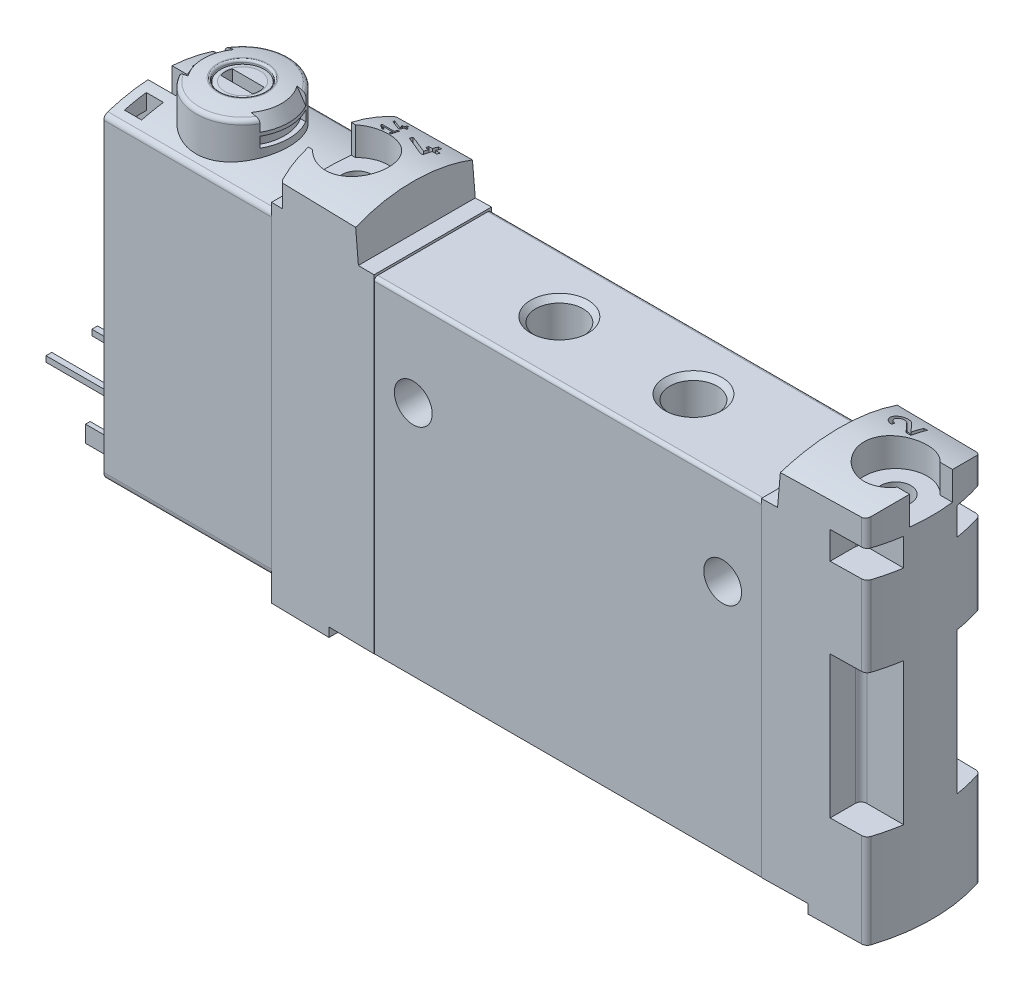
SolidWorks part; units mm, degrees
ref_plane "Front Plane" through (0, 0, 0) normal (0, 0, 1) x (1, 0, 0)
ref_plane "Top Plane" through (0, 0, 0) normal (0, 1, 0) x (1, 0, 0)
ref_plane "Right Plane" through (0, 0, 0) normal (1, 0, 0) x (0, 0, -1)
sketch "Sketch1" plane through (0, 0, 0) normal (1, 0, 0) x (0, 0, -1)
  line L0 (-5.1, 28.15) -> (-5.1, 0)
  line L1 (-5.1, 0) -> (5.1, 0)
  line L2 (5.1, 0) -> (5.1, 28.15)
  line L3 (4.8, 28.45) -> (-4.8, 28.45)
  arc A0 (5.1, 28.15) -> (4.8, 28.45) centre (4.8, 28.15) ccw
  arc A1 (-4.8, 28.45) -> (-5.1, 28.15) centre (-4.8, 28.15) ccw
extrude "Boss-Extrude1" add sketch "Sketch1" against normal blind 16.9 and the other way blind 16.9
sketch "Sketch2" plane through (0, 0, 0) normal (0, 0, 1) x (1, 0, 0)
  circle A0 centre (-13.5, 20.65) radius 1.65
extrude "Cut-Extrude1" cut sketch "Sketch2" along normal blind 6 and the other way blind 6
sketch "Sketch3" plane through (0, 0, 0) normal (0, 0, 1) x (1, 0, 0)
  circle A0 centre (13.5, 20.65) radius 1.65
extrude "Cut-Extrude2" cut sketch "Sketch3" along normal blind 6 and the other way blind 6
ref_plane "Plane1" through (0, 0, 0) normal (0, 0, 1) x (1, 0, 0)
ref_plane "Plane2" through (0, 0, -1.55) normal (0, 0, 1) x (1, 0, 0)
ref_plane "Plane3" through (0, 0, 1.55) normal (0, 0, 1) x (1, 0, 0)
ref_plane "Plane4" through (-13.4, 0, 0) normal (1, 0, 0) x (0, 0, -1)
ref_plane "Plane5" through (0, 0, 1.495) normal (0, 0, 1) x (1, 0, 0)
ref_plane "Plane6" through (0, 0, -2.205) normal (0, 0, 1) x (1, 0, 0)
hole_wizard "Hole1" positions "Sketch5" profile "Sketch4" legacy
sketch "Sketch5" plane through (0, 0, 0) normal (0, -1, 0) x (-1, 0, 0)
  point P0 (-11, 0)
sketch "Sketch4" plane through (11, 0, 0) normal (1, 0, 0) x (0, 0, -1)
  line L0 (0, 0) -> (0, 13.5)
  line L1 (0, 13.5) -> (2.067, 13.5)
  line L2 (2.067, 13.5) -> (2.067, 0.433)
  line L3 (2.067, 0.433) -> (2.5, 0)
  line L4 (2.5, 0) -> (0, 0)
  line L5 (0, -6.4453) -> (0, 115.525) construction
  line L6 (-2.067, 0.433) -> (-2.5, 0) construction
  dimension "Diameter" = 4.134
  dimension "Depth" = 13.5
  dimension "C-Sink Angle" = 90
  dimension "C-Sink Diameter" = 5
cosmetic thread "Cosmetic Thread1" parameters "D1"=5, "D2"=5
hole_wizard "Hole2" positions "Sketch7" profile "Sketch6" legacy
sketch "Sketch7" plane through (0, 0, 0) normal (0, -1, 0) x (-1, 0, 0)
  point P0 (0, 0)
sketch "Sketch6" plane through (0, 0, 0) normal (1, 0, 0) x (0, 0, -1)
  line L0 (0, 0) -> (0, 19.9934)
  line L1 (0, 19.9934) -> (2.067, 18.8)
  line L2 (2.067, 18.8) -> (2.067, 0.433)
  line L3 (2.067, 0.433) -> (2.5, 0)
  line L4 (2.5, 0) -> (0, 0)
  line L5 (0, -14.3089) -> (0, 102.4216) construction
  line L6 (0, 19.9934) -> (-2.067, 18.8) construction
  line L7 (-2.067, 0.433) -> (-2.5, 0) construction
  dimension "Diameter" = 4.134
  dimension "Depth" = 18.8
  dimension "C-Sink Diameter" = 5
  dimension "C-Sink Angle" = 90
  dimension "Drill Angle" = 120
cosmetic thread "Cosmetic Thread2" parameters "D1"=5, "D2"=5
hole_wizard "Hole3" positions "Sketch9" profile "Sketch8" legacy
sketch "Sketch9" plane through (0, 0, 0) normal (0, -1, 0) x (-1, 0, 0)
  point P0 (11, 0)
sketch "Sketch8" plane through (-11, 0, 0) normal (1, 0, 0) x (0, 0, -1)
  line L0 (0, 0) -> (0, 13.5)
  line L1 (0, 13.5) -> (2.067, 13.5)
  line L2 (2.067, 13.5) -> (2.067, 0.433)
  line L3 (2.067, 0.433) -> (2.5, 0)
  line L4 (2.5, 0) -> (0, 0)
  line L5 (0, -6.4453) -> (0, 115.525) construction
  line L6 (-2.067, 0.433) -> (-2.5, 0) construction
  dimension "Diameter" = 4.134
  dimension "Depth" = 13.5
  dimension "C-Sink Angle" = 90
  dimension "C-Sink Diameter" = 5
cosmetic thread "Cosmetic Thread3" parameters "D1"=5, "D2"=5
hole_wizard "Hole4" positions "Sketch11" profile "Sketch10" legacy
sketch "Sketch11" plane through (0, 28.45, 0) normal (0, 1, 0) x (1, 0, 0)
  point P0 (-5.85, 0)
sketch "Sketch10" plane through (-5.85, 28.45, 0) normal (1, 0, 0) x (0, 0, 1)
  line L0 (0, 0) -> (0, 6.6)
  line L1 (0, 6.6) -> (2.067, 6.6)
  line L2 (2.067, 6.6) -> (2.067, 0.433)
  line L3 (2.067, 0.433) -> (2.5, 0)
  line L4 (2.5, 0) -> (0, 0)
  line L5 (0, -6.4453) -> (0, 115.525) construction
  line L6 (-2.067, 0.433) -> (-2.5, 0) construction
  dimension "Diameter" = 4.134
  dimension "Depth" = 6.6
  dimension "C-Sink Angle" = 90
  dimension "C-Sink Diameter" = 5
cosmetic thread "Cosmetic Thread4" parameters "D1"=5.8, "D2"=5
hole_wizard "Hole5" positions "Sketch13" profile "Sketch12" legacy
sketch "Sketch13" plane through (0, 28.45, 0) normal (0, 1, 0) x (1, 0, 0)
  point P0 (5.85, 0)
sketch "Sketch12" plane through (5.85, 28.45, 0) normal (1, 0, 0) x (0, 0, 1)
  line L0 (0, 0) -> (0, 6.6)
  line L1 (0, 6.6) -> (2.067, 6.6)
  line L2 (2.067, 6.6) -> (2.067, 0.433)
  line L3 (2.067, 0.433) -> (2.5, 0)
  line L4 (2.5, 0) -> (0, 0)
  line L5 (0, -6.4453) -> (0, 115.525) construction
  line L6 (-2.067, 0.433) -> (-2.5, 0) construction
  dimension "Diameter" = 4.134
  dimension "Depth" = 6.6
  dimension "C-Sink Angle" = 90
  dimension "C-Sink Diameter" = 5
cosmetic thread "Cosmetic Thread5" parameters "D1"=5.8, "D2"=5
ref_plane "Plane7" through (0, 20.4, 0) normal (0, 1, 0) x (1, 0, 0)
ref_plane "Plane8" through (-11.06, 0, 0) normal (1, 0, 0) x (0, 0, -1)
ref_plane "Plane9" through (-4.15, 0, 0) normal (1, 0, 0) x (0, 0, -1)
ref_plane "Plane10" through (3.15, 0, 0) normal (1, 0, 0) x (0, 0, -1)
ref_plane "Plane11" through (0, 0, -3) normal (0, 0, 1) x (1, 0, 0)
hole_wizard "Hole6" positions "Sketch15" profile "Sketch14" legacy
sketch "Sketch15" plane through (0, 0, 0) normal (0, -1, 0) x (-1, 0, 0)
  point P0 (4.9, 3)
sketch "Sketch14" plane through (-4.9, 0, -3) normal (1, 0, 0) x (0, 0, -1)
  line L0 (0, 0) -> (0, 2.2217)
  line L1 (0, 2.2217) -> (1.25, 1.5)
  line L2 (1.25, 1.5) -> (1.25, 0)
  line L4 (1.25, 0) -> (0, 0)
  line L6 (0, 2.2217) -> (-1.25, 1.5) construction
  line L7 (0, -4.2442) -> (0, 117.3081) construction
  dimension "Diameter" = 2.5
  dimension "Depth" = 1.5
  dimension "Drill Angle" = 120
ref_plane "Plane12" through (0, -0.8, 0) normal (0, 1, 0) x (1, 0, 0)
sketch "Sketch16" plane through (0, -0.8, 0) normal (0, 1, 0) x (1, 0, 0)
  line L0 (16.9, 5.125) -> (16.9, -5.125)
  line L1 (16.9, -5.125) -> (25.5086, -4.9747)
  line L2 (25.5086, 4.9747) -> (16.9, 5.125)
  arc A0 (25.5086, -4.9747) -> (25.976, -4.6275) centre (25.4999, -4.4748) ccw
  arc A1 (25.976, -4.6275) -> (25.976, 4.6275) centre (11.55, 0) ccw
  arc A2 (25.976, 4.6275) -> (25.5086, 4.9747) centre (25.4999, 4.4748) ccw
extrude "Boss-Extrude2" add sketch "Sketch16" along normal blind 33.1
ref_plane "Plane13" through (0, 7.4, 0) normal (0, 1, 0) x (1, 0, 0)
sketch "Sketch17" plane through (0, 7.4, 0) normal (0, 1, 0) x (1, 0, 0)
  line L0 (23.3, 2.325) -> (27.8, 2.325)
  line L1 (27.8, 2.325) -> (27.8, -2.325)
  line L2 (27.8, -2.325) -> (23.3, -2.325)
  line L3 (22.8, -2.825) -> (22.8, -5.125)
  line L4 (22.8, -5.125) -> (29.8, -5.125)
  line L5 (29.8, -5.125) -> (29.8, 5.125)
  line L6 (29.8, 5.125) -> (22.8, 5.125)
  line L7 (22.8, 5.125) -> (22.8, 2.825)
  arc A0 (22.8, 2.825) -> (23.3, 2.325) centre (23.3, 2.825) ccw
  arc A1 (23.3, -2.325) -> (22.8, -2.825) centre (23.3, -2.825) ccw
extrude "Cut-Extrude3" cut sketch "Sketch17" along normal blind 12.4
ref_plane "Plane14" through (0, 26.8, 0) normal (0, 1, 0) x (1, 0, 0)
sketch "Sketch18" plane through (0, 26.8, 0) normal (0, 1, 0) x (1, 0, 0)
  line L0 (23.3, 2.325) -> (27.8, 2.325)
  line L1 (27.8, 2.325) -> (27.8, -2.325)
  line L2 (27.8, -2.325) -> (23.3, -2.325)
  line L3 (22.8, -2.825) -> (22.8, -5.125)
  line L4 (22.8, -5.125) -> (29.8, -5.125)
  line L5 (29.8, -5.125) -> (29.8, 5.125)
  line L6 (29.8, 5.125) -> (22.8, 5.125)
  line L7 (22.8, 5.125) -> (22.8, 2.825)
  arc A0 (22.8, 2.825) -> (23.3, 2.325) centre (23.3, 2.825) ccw
  arc A1 (23.3, -2.325) -> (22.8, -2.825) centre (23.3, -2.825) ccw
extrude "Cut-Extrude4" cut sketch "Sketch18" along normal blind 2.4
ref_plane "Plane15" through (0, 28.45, 0) normal (0, 1, 0) x (1, 0, 0)
sketch "Sketch19" plane through (0, 0, 0) normal (1, 0, 0) x (0, 0, -1)
  line L0 (5.125, 31.3973) -> (5.125, 37)
  line L1 (5.125, 37) -> (-5.125, 37)
  line L2 (-5.125, 37) -> (-5.125, 31.3973)
  arc A0 (-5.125, 31.3973) -> (5.125, 31.3973) centre (0, 17.3) cw
ref_plane "Plane16" through (0, 29.5, 0) normal (0, 1, 0) x (1, 0, 0)
sketch "Sketch20" plane through (0, 0, 0) normal (0, 0, 1) x (1, 0, 0)
  line L0 (13.29, 34.65) -> (13.29, 28.65)
  line L1 (13.29, 28.65) -> (18.29, 28.65)
  line L2 (18.29, 28.65) -> (18.8149, 34.65)
  line L3 (18.8149, 34.65) -> (13.29, 34.65)
extrude "Cut-Extrude5" cut sketch "Sketch20" along normal blind 6 and the other way blind 6
ref_plane "Plane17" through (21.86, 0, 0) normal (1, 0, 0) x (0, 0, -1)
ref_plane "Plane18" through (0, 14.6, 0) normal (0, 1, 0) x (1, 0, 0)
ref_plane "Plane19" through (40.24, 0, 0) normal (1, 0, 0) x (0, 0, -1)
ref_plane "Plane20" through (0, 10.65, 0) normal (0, 1, 0) x (1, 0, 0)
sketch "Sketch21" plane through (0, 0, 0) normal (0, 0, 1) x (1, 0, 0)
  line L0 (23.5, 29.7) -> (24.825, 29.7)
  line L1 (24.825, 29.7) -> (24.625, -0.8)
  line L2 (24.625, -0.8) -> (23.5, -0.8)
  line L3 (23.5, -0.8) -> (23.5, 29.7)
  line L4 (23.5, -0.8) -> (23.5, 29.7) construction
revolve "Cut-Revolve1" cut sketch "Sketch21" angle 360 about L4 reverse direction yes
ref_plane "Plane21" through (0, 29.7, 0) normal (0, 1, 0) x (1, 0, 0)
sketch "Sketch22" plane through (0, 29.7, 0) normal (0, 1, 0) x (1, 0, 0)
  line L0 (25.5117, -1.875) -> (28.5, -1.875)
  line L1 (28.5, -1.875) -> (28.5, 1.875)
  line L2 (28.5, 1.875) -> (25.5117, 1.875)
  arc A0 (25.5117, 1.875) -> (25.5117, -1.875) centre (23.5, 0) ccw
extrude "Cut-Extrude6" cut sketch "Sketch22" along normal blind 4
ref_plane "Plane22" through (0, -0.8, 0) normal (0, 1, 0) x (1, 0, 0)
sketch "Sketch23" plane through (0, -0.8, 0) normal (0, 1, 0) x (1, 0, 0)
  line L0 (-26, -4.9662) -> (-16.9, -5.125)
  line L1 (-16.9, -5.125) -> (-16.9, 5.125)
  line L2 (-16.9, 5.125) -> (-26, 4.9662)
  line L3 (-26, 4.9662) -> (-26, -4.9662)
extrude "Boss-Extrude3" add sketch "Sketch23" along normal blind 33.1
extrude "Cut-Extrude7" cut sketch "Sketch19" along normal blind 32 and the other way blind 32
sketch "Sketch24" plane through (0, 29.7, 0) normal (0, 1, 0) x (1, 0, 0)
  line L0 (-26.5, -1.875) -> (-25.5117, -1.875)
  line L1 (-25.5117, 1.875) -> (-26.5, 1.875)
  line L2 (-26.5, 1.875) -> (-26.5, -1.875)
  arc A0 (-25.5117, -1.875) -> (-25.5117, 1.875) centre (-23.5, 0) ccw
extrude "Cut-Extrude8" cut sketch "Sketch24" along normal blind 4
sketch "Sketch25" plane through (0, 0, 0) normal (0, 0, 1) x (1, 0, 0)
  line L0 (-18.8149, 34.65) -> (-18.29, 28.65)
  line L1 (-18.29, 28.65) -> (-13.29, 28.65)
  line L2 (-13.29, 28.65) -> (-13.29, 34.65)
  line L3 (-13.29, 34.65) -> (-18.8149, 34.65)
extrude "Cut-Extrude9" cut sketch "Sketch25" along normal blind 6 and the other way blind 6
sketch "Sketch26" plane through (0, 29.5, 0) normal (0, 1, 0) x (1, 0, 0)
  line L0 (-31.04, -6.125) -> (-21.04, -6.125)
  line L1 (-21.04, -6.125) -> (-21.04, -5.125)
  line L2 (-21.04, -5.125) -> (-24.7731, -5.0598)
  line L3 (-24.7731, 5.0598) -> (-21.04, 5.125)
  line L4 (-21.04, 5.125) -> (-21.04, 6.125)
  line L5 (-21.04, 6.125) -> (-31.04, 6.125)
  line L6 (-31.04, 6.125) -> (-31.04, -6.125)
  arc A0 (-24.7731, -5.0598) -> (-25.239, -4.7172) centre (-24.7643, -4.5599) cw
  arc A1 (-25.239, -4.7172) -> (-25.239, 4.7172) centre (-11, 0) cw
  arc A2 (-25.239, 4.7172) -> (-24.7731, 5.0598) centre (-24.7643, 4.5599) cw
extrude "Cut-Extrude10" cut sketch "Sketch26" along normal blind 5
sketch "Sketch27" plane through (0, 0, 0) normal (0, 0, 1) x (1, 0, 0)
  line L0 (-20.9, -2) -> (20.9, -2)
  line L1 (20.9, -2) -> (20.9, 0)
  line L2 (20.9, 0) -> (-20.9, 0)
  line L3 (-20.9, 0) -> (-20.9, -2)
extrude "Cut-Extrude11" cut sketch "Sketch27" along normal blind 8 and the other way blind 8
ref_plane "Plane23" through (-21.86, 0, 0) normal (1, 0, 0) x (0, 0, -1)
sketch "Sketch28" plane through (-21.86, 0, 0) normal (1, 0, 0) x (0, 0, -1)
  line L0 (-4.2, 1) -> (4.2, 1)
  line L1 (4.9, 1.7) -> (4.9, 28.3163)
  line L2 (-4.9, 28.3163) -> (-4.9, 1.7)
  arc A0 (-4.9, 1.7) -> (-4.2, 1) centre (-4.2, 1.7) ccw
  arc A1 (4.2, 1) -> (4.9, 1.7) centre (4.2, 1.7) ccw
  arc A2 (4.9, 28.3163) -> (4.5517, 28.7927) centre (4.4, 28.3163) ccw
  arc A3 (4.5517, 28.7927) -> (-4.5517, 28.7927) centre (0, 14.5) ccw
  arc A4 (-4.5517, 28.7927) -> (-4.9, 28.3163) centre (-4.4, 28.3163) ccw
extrude "Boss-Extrude4" add sketch "Sketch28" against normal blind 21.34
ref_plane "Plane24" through (-40.7, 0, 0) normal (1, 0, 0) x (0, 0, -1)
sketch "Sketch29" plane through (-40.7, 0, 0) normal (1, 0, 0) x (0, 0, -1)
  line L0 (-4.9, 31) -> (-4.9, 1)
  line L1 (-4.9, 1) -> (4.9, 1)
  line L2 (4.9, 1) -> (4.9, 31)
  line L3 (4.9, 31) -> (-4.9, 31)
  line L4 (-4, 2.2) -> (-3.55, 1.75)
  line L5 (-3.55, 1.75) -> (3.55, 1.75)
  line L6 (3.55, 1.75) -> (4, 2.2)
  line L7 (4, 2.2) -> (4, 3.65)
  line L8 (4, 3.65) -> (3.6, 3.65)
  line L9 (3.6, 3.65) -> (3.6, 2.95)
  line L10 (3.1, 2.45) -> (-3.1, 2.45)
  line L11 (-3.6, 2.95) -> (-3.6, 3.65)
  line L12 (-3.6, 3.65) -> (-4, 3.65)
  line L13 (-4, 3.65) -> (-4, 2.2)
  arc A0 (3.6, 2.95) -> (3.1, 2.45) centre (3.1, 2.95) cw
  arc A1 (-3.1, 2.45) -> (-3.6, 2.95) centre (-3.1, 2.95) cw
extrude "Cut-Extrude12" cut sketch "Sketch29" against normal blind 6
sketch "Sketch30" plane through (0, 0, 0) normal (0, 0, 1) x (1, 0, 0)
  line L0 (-43.2, 1.75) -> (-42.1277, 1.25)
  line L1 (-42.1277, 1.25) -> (-41.9, 1.25)
  line L2 (-41.9, 1.25) -> (-41.9, 1.75)
  line L3 (-41.9, 1.75) -> (-43.2, 1.75)
extrude "Boss-Extrude5" add sketch "Sketch30" against normal blind 1.2 and the other way blind 1.2
sketch "Sketch31" plane through (-40.7, 0, 0) normal (1, 0, 0) x (0, 0, -1)
  line L0 (-3.15, 14.1) -> (-3.15, 3.1)
  line L1 (-3.15, 3.1) -> (3.15, 3.1)
  line L2 (3.15, 3.1) -> (3.15, 14.1)
  line L3 (3.15, 14.1) -> (-3.15, 14.1)
extrude "Boss-Extrude6" add sketch "Sketch31" against normal blind 1
sketch "Sketch32" plane through (-40.7, 0, 0) normal (1, 0, 0) x (0, 0, -1)
  line L0 (-2.25, 5.35) -> (-2.25, 4.85)
  line L1 (-2.25, 4.85) -> (-1.75, 4.85)
  line L2 (-1.75, 4.85) -> (-1.75, 5.35)
  line L3 (-1.75, 5.35) -> (-2.25, 5.35)
extrude "Boss-Extrude7" add sketch "Sketch32" against normal blind 7.7
sketch "Sketch33" plane through (-40.7, 0, 0) normal (1, 0, 0) x (0, 0, -1)
  line L0 (1.75, 5.35) -> (1.75, 4.85)
  line L1 (1.75, 4.85) -> (2.25, 4.85)
  line L2 (2.25, 4.85) -> (2.25, 5.35)
  line L3 (2.25, 5.35) -> (1.75, 5.35)
extrude "Boss-Extrude8" add sketch "Sketch33" against normal blind 7.7
ref_plane "Plane25" through (-40.24, 0, 0) normal (1, 0, 0) x (0, 0, -1)
hole_wizard "Hole7" positions "Sketch35" profile "Sketch34" legacy
sketch "Sketch35" plane through (0, 29.7, 0) normal (0, 1, 0) x (1, 0, 0)
  point P0 (-23.5, 0)
sketch "Sketch34" plane through (-23.5, 29.7, 0) normal (1, 0, 0) x (0, 0, 1)
  line L0 (0, 0) -> (0, 30.5)
  line L1 (0, 30.5) -> (1.125, 30.5)
  line L2 (1.125, 30.5) -> (1.325, 0)
  line L3 (1.325, 0) -> (0, 0)
  line L4 (0, 110) -> (0, -10) construction
  dimension "Minor Diameter" = 2.25
  dimension "Depth" = 30.5
  dimension "Major Diameter" = 2.65
sketch "Sketch36" plane through (0, 0, 0) normal (0, 0, 1) x (1, 0, 0)
  line L0 (-33.5, 32.665) -> (-29.45, 32.665)
  line L1 (-29.45, 32.665) -> (-29.45, 27.365)
  line L2 (-29.45, 27.365) -> (-33.5, 27.365)
  line L3 (-33.5, 27.365) -> (-33.5, 32.665)
  line L4 (-33.5, 27.365) -> (-33.5, 32.665) construction
revolve "Revolve1" add sketch "Sketch36" angle 360 about L4 reverse direction yes
ref_plane "Plane26" through (0, 30.1, 0) normal (0, 1, 0) x (1, 0, 0)
sketch "Sketch37" plane through (0, 30.1, 0) normal (0, 1, 0) x (1, 0, 0)
  line L0 (-28.9174, -2) -> (-30.7505, -2)
  line L1 (-30.7505, 2) -> (-28.9174, 2)
  line L2 (-38.0826, 2) -> (-36.2495, 2)
  line L3 (-36.2495, -2) -> (-38.0826, -2)
  circle A0 centre (-33.5, 0) radius 6
  arc A1 (-38.0826, -2) -> (-28.9174, -2) centre (-33.5, 0) ccw
  arc A2 (-30.7505, -2) -> (-30.7505, 2) centre (-33.5, 0) ccw
  arc A3 (-28.9174, 2) -> (-38.0826, 2) centre (-33.5, 0) ccw
  arc A4 (-36.2495, 2) -> (-36.2495, -2) centre (-33.5, 0) ccw
extrude "Cut-Extrude13" cut sketch "Sketch37" along normal blind 3
sketch "Sketch38" plane through (0, 0, 0) normal (0, 0, 1) x (1, 0, 0)
  line L0 (-30.1, 32.4408) -> (-30.1, 27.365)
  line L1 (-30.1, 27.365) -> (-29.45, 27.365)
  line L2 (-29.45, 27.365) -> (-29.45, 30.115)
  line L3 (-29.45, 30.115) -> (-29.85, 30.115)
  line L4 (-29.85, 30.115) -> (-29.85, 31.015)
  line L5 (-29.85, 31.015) -> (-29.45, 31.015)
  line L6 (-29.45, 31.015) -> (-29.45, 31.315)
  line L7 (-29.45, 31.315) -> (-30.1, 32.4408)
  line L8 (-33.5, 27.365) -> (-33.5, 32.665) construction
revolve "Revolve2" add sketch "Sketch38" angle 360 about L8 reverse direction yes
sketch "Sketch39" plane through (0, 0, 0) normal (0, 0, 1) x (1, 0, 0)
  line L0 (-33.5, 33.365) -> (-28.5, 33.365)
  line L1 (-28.5, 33.365) -> (-28.5, 29.865)
  line L2 (-28.5, 29.865) -> (-29.45, 29.865)
  line L3 (-29.45, 29.865) -> (-29.45, 31.9614)
  line L4 (-31.55, 32.468) -> (-31.55, 31.295)
  line L5 (-31.55, 31.295) -> (-33.5, 31.295)
  line L6 (-33.5, 31.295) -> (-33.5, 33.365)
  line L7 (-33.5, 31.295) -> (-33.5, 33.365) construction
  arc A0 (-29.45, 31.9614) -> (-29.75, 32.3487) centre (-29.85, 31.9614) ccw
  arc A1 (-29.75, 32.3487) -> (-31.3209, 32.6659) centre (-33.5, 17.825) ccw
  arc A2 (-31.3209, 32.6659) -> (-31.55, 32.468) centre (-31.35, 32.468) ccw
revolve "Cut-Revolve2" cut sketch "Sketch39" angle 360 about L7 reverse direction yes
sketch "Sketch40" plane through (0, 0, 0) normal (0, 0, 1) x (1, 0, 0)
  line L0 (-33.5, 32.41) -> (-31.9558, 32.41)
  line L1 (-31.9558, 32.41) -> (-31.6, 32.36)
  line L2 (-31.6, 32.36) -> (-31.6, 30.71)
  line L3 (-31.1, 30.21) -> (-30.95, 30.21)
  line L4 (-30.95, 30.21) -> (-30.95, 26.41)
  line L5 (-30.95, 26.41) -> (-33.5, 26.41)
  line L6 (-33.5, 26.41) -> (-33.5, 32.41)
  line L7 (-33.5, 26.41) -> (-33.5, 32.41) construction
  arc A0 (-31.6, 30.71) -> (-31.1, 30.21) centre (-31.1, 30.71) ccw
revolve "Revolve3" add sketch "Sketch40" angle 360 about L7 reverse direction yes
ref_plane "Plane27" through (0, 32.41, 0) normal (0, 1, 0) x (1, 0, 0)
sketch "Sketch41" plane through (0, 32.41, 0) normal (0, 1, 0) x (1, 0, 0)
  line L0 (-34.893, -0.5) -> (-32.107, -0.5)
  line L1 (-32.107, 0.5) -> (-34.893, 0.5)
  arc A0 (-34.893, 0.5) -> (-34.893, -0.5) centre (-33.5, 0) ccw
  arc A1 (-32.107, -0.5) -> (-32.107, 0.5) centre (-33.5, 0) ccw
extrude "Cut-Extrude14" cut sketch "Sketch41" against normal blind 2.15
ref_plane "Plane28" through (0, 0, -1.605) normal (0, 0, 1) x (1, 0, 0)
ref_plane "Plane29" through (0, 17.4, 0) normal (0, 1, 0) x (1, 0, 0)
ref_plane "Plane30" through (0, 1.2, 0) normal (0, 1, 0) x (1, 0, 0)
sketch "Sketch42" plane through (0, 0, 0) normal (0, 0, 1) x (1, 0, 0)
  line L0 (-45.796, 29.534) -> (-45.796, 18.4808)
  line L1 (-45.796, 18.4808) -> (-38.296, 24.774)
  line L2 (-38.296, 24.774) -> (-38.296, 29.534)
  line L3 (-38.296, 29.534) -> (-45.796, 29.534)
extrude "Cut-Extrude15" cut sketch "Sketch42" along normal blind 1.05 and the other way blind 1.05
ref_plane "Plane31" through (0, 32.66, 0) normal (0, 1, 0) x (1, 0, 0)
ref_plane "Plane32" through (-45.936, 0, 0) normal (1, 0, 0) x (0, 0, -1)
ref_plane "Plane33" through (43.24, 0, 0) normal (1, 0, 0) x (0, 0, -1)
ref_plane "Plane34" through (-43.24, 0, 0) normal (1, 0, 0) x (0, 0, -1)
ref_plane "Plane35" through (-38.4, 0, 0) normal (1, 0, 0) x (0, 0, -1)
sketch "Sketch43" plane through (-38.4, 0, 0) normal (1, 0, 0) x (0, 0, -1)
  line L0 (-3.9, 31) -> (-3.9, 25)
  line L1 (-3.9, 25) -> (-2, 25)
  line L2 (-2, 25) -> (-2, 30)
  line L3 (-2, 30) -> (2, 30)
  line L4 (2, 30) -> (2, 25)
  line L5 (2, 25) -> (3.9, 25)
  line L6 (3.9, 25) -> (3.9, 31)
  line L7 (3.9, 31) -> (-3.9, 31)
extrude "Cut-Extrude16" cut sketch "Sketch43" against normal blind 1.5
sketch "Sketch44" plane through (-38.4, 0, 0) normal (1, 0, 0) x (0, 0, -1)
  line L0 (-3.9, 28) -> (-3.9, 25)
  line L1 (-3.9, 25) -> (-2, 25)
  line L2 (-2, 25) -> (-2, 28)
  line L3 (-2, 28) -> (-3.9, 28)
extrude "Cut-Extrude17" cut sketch "Sketch44" against normal blind 3
sketch "Sketch45" plane through (-38.4, 0, 0) normal (1, 0, 0) x (0, 0, -1)
  line L0 (2, 28) -> (2, 25)
  line L1 (2, 25) -> (3.9, 25)
  line L2 (3.9, 25) -> (3.9, 28)
  line L3 (3.9, 28) -> (2, 28)
extrude "Cut-Extrude18" cut sketch "Sketch45" against normal blind 3
ref_plane "Plane36" through (0, 31.7, 0) normal (0, 1, 0) x (1, 0, 0)
sketch "Sketch46" plane through (0, 31.7, 0) normal (0, 1, 0) x (1, 0, 0)
  line L0 (-24.64, 3.175) -> (-24.178, 2.8515)
  line L1 (-24.178, 2.8515) -> (-24.1076, 2.9522)
  line L2 (-24.1076, 2.9522) -> (-24.4258, 3.175)
  line L3 (-24.4258, 3.175) -> (-23.59, 3.175)
  line L4 (-23.59, 3.175) -> (-23.59, 2.875)
  line L5 (-23.59, 2.875) -> (-23.44, 2.875)
  line L6 (-23.44, 2.875) -> (-23.44, 3.625)
  line L7 (-23.44, 3.625) -> (-23.59, 3.625)
  line L8 (-23.59, 3.625) -> (-23.59, 3.325)
  line L9 (-23.59, 3.325) -> (-24.64, 3.325)
  line L10 (-24.64, 3.325) -> (-24.64, 3.175)
extrude "Cut-Extrude19" cut sketch "Sketch46" along normal blind 1 and the other way blind 1
sketch "Sketch47" plane through (0, 31.7, 0) normal (0, 1, 0) x (1, 0, 0)
  line L0 (-24.64, 4.2508) -> (-23.7483, 3.835)
  line L1 (-23.7483, 3.835) -> (-23.64, 3.835)
  line L2 (-23.64, 3.835) -> (-23.64, 4.25)
  line L3 (-23.64, 4.25) -> (-23.44, 4.25)
  line L4 (-23.44, 4.25) -> (-23.44, 4.4)
  line L5 (-23.44, 4.4) -> (-23.64, 4.4)
  line L6 (-23.64, 4.4) -> (-23.64, 4.665)
  line L7 (-23.64, 4.665) -> (-23.79, 4.665)
  line L8 (-23.79, 4.665) -> (-23.79, 4.4)
  line L9 (-23.79, 4.4) -> (-23.94, 4.4)
  line L10 (-23.94, 4.4) -> (-23.94, 4.25)
  line L11 (-23.94, 4.25) -> (-23.79, 4.25)
  line L12 (-23.79, 4.25) -> (-23.79, 4.0199)
  line L13 (-23.79, 4.0199) -> (-24.64, 4.4163)
  line L14 (-24.64, 4.4163) -> (-24.64, 4.2508)
extrude "Cut-Extrude20" cut sketch "Sketch47" along normal blind 1 and the other way blind 1
sketch "Sketch48" plane through (0, 31.7, 0) normal (0, 1, 0) x (1, 0, 0)
  line L0 (-22.44, 3.5016) -> (-20.6566, 2.67)
  line L1 (-20.6566, 2.67) -> (-20.44, 2.67)
  line L2 (-20.44, 2.67) -> (-20.44, 3.5)
  line L3 (-20.44, 3.5) -> (-20.04, 3.5)
  line L4 (-20.04, 3.5) -> (-20.04, 3.8)
  line L5 (-20.04, 3.8) -> (-20.44, 3.8)
  line L6 (-20.44, 3.8) -> (-20.44, 4.33)
  line L7 (-20.44, 4.33) -> (-20.74, 4.33)
  line L8 (-20.74, 4.33) -> (-20.74, 3.8)
  line L9 (-20.74, 3.8) -> (-21.04, 3.8)
  line L10 (-21.04, 3.8) -> (-21.04, 3.5)
  line L11 (-21.04, 3.5) -> (-20.74, 3.5)
  line L12 (-20.74, 3.5) -> (-20.74, 3.0399)
  line L13 (-20.74, 3.0399) -> (-22.44, 3.8326)
  line L14 (-22.44, 3.8326) -> (-22.44, 3.5016)
extrude "Cut-Extrude21" cut sketch "Sketch48" along normal blind 1 and the other way blind 1
sketch "Sketch49" plane through (0, 31.7, 0) normal (0, 1, 0) x (1, 0, 0)
  line L0 (20.365, 2.775) -> (20.365, 3.075)
  line L1 (20.6749, 3.7909) -> (21.6285, 2.775)
  line L2 (21.6285, 2.775) -> (22.04, 2.775)
  line L3 (22.04, 2.775) -> (22.04, 4.225)
  line L4 (22.04, 4.225) -> (21.74, 4.225)
  line L5 (21.74, 4.225) -> (21.74, 3.0946)
  line L6 (21.74, 3.0946) -> (20.8936, 3.9962)
  arc A0 (20.8936, 3.9962) -> (20.365, 2.775) centre (20.365, 3.5) ccw
  arc A1 (20.365, 3.075) -> (20.6749, 3.7909) centre (20.365, 3.5) cw
extrude "Cut-Extrude22" cut sketch "Sketch49" along normal blind 1 and the other way blind 1
ref_plane "DICHTUNG XY" through (0, 0, 0) normal (0, 1, 0) x (1, 0, 0)
ref_plane "DICHTUNG XZ" through (0, 0, 0) normal (0, 0, 1) x (1, 0, 0)
ref_plane "DICHTUNG YZ" through (0, 0, 0) normal (1, 0, 0) x (0, 0, -1)
ref_axis "DICHTUNG X" through (-80.9, 0, 0) along (1, 0, 0)
ref_axis "DICHTUNG Y" through (0, 0, 50) along (0, 0, -1)
ref_axis "DICHTUNG Z" through (0, 50, 0) along (0, -1, 0)
sketch3d "DICHTUNG"
  point P0 (0, 0, 0)
ref_plane "GEHAUSE XY" through (0, 0, 0) normal (0, 1, 0) x (1, 0, 0)
ref_plane "GEHAUSE XZ" through (0, 0, 0) normal (0, 0, 1) x (1, 0, 0)
ref_plane "GEHAUSE YZ" through (0, 0, 0) normal (1, 0, 0) x (0, 0, -1)
ref_axis "GEHAUSE X" through (-80.9, 0, 0) along (1, 0, 0)
ref_axis "GEHAUSE Y" through (0, 0, 50) along (0, 0, -1)
ref_axis "GEHAUSE Z" through (0, 50, 0) along (0, -1, 0)
sketch3d "GEHAUSE"
  point P0 (0, 0, 0)
ref_plane "HHB2 XY" through (0, 32.66, 0) normal (0, 1, 0) x (1, 0, 0)
ref_plane "HHB2 XZ" through (0, 0, 0) normal (0, 0, 1) x (1, 0, 0)
ref_plane "HHB2 YZ" through (-33.5, 0, 0) normal (1, 0, 0) x (0, 0, -1)
ref_axis "HHB2 X" through (-80.9, 32.66, 0) along (1, 0, 0)
ref_axis "HHB2 Y" through (-33.5, 32.66, 50) along (0, 0, -1)
ref_axis "HHB2 Z" through (-33.5, 50, 0) along (0, -1, 0)
sketch3d "HHB2"
  point P0 (-33.5, 32.66, 0)
ref_plane "NEBV2 XY" through (-45.936, 0, 0) normal (-1, 0, 0) x (0, 0, 1)
ref_plane "NEBV2 XZ" through (0, 24.712, 0) normal (0, 1, 0) x (1, 0, 0)
ref_plane "NEBV2 YZ" through (0, 0, 0) normal (0, 0, -1) x (-1, 0, 0)
ref_axis "NEBV2 X" through (-45.936, 24.712, 80.9) along (0, 0, -1)
ref_axis "NEBV2 Y" through (-45.936, 50, 0) along (0, -1, 0)
ref_axis "NEBV2 Z" through (-80.9, 24.712, 0) along (1, 0, 0)
sketch3d "NEBV2"
  point P0 (-45.936, 24.712, 0)
ref_plane "QS_K1 XY" through (0, 0, 0) normal (0, 1, 0) x (1, 0, 0)
ref_plane "QS_K1 XZ" through (0, 0, 0) normal (0, 0, 1) x (1, 0, 0)
ref_plane "QS_K1 YZ" through (0, 0, 0) normal (1, 0, 0) x (0, 0, -1)
ref_axis "QS_K1 X" through (-80.9, 0, 0) along (1, 0, 0)
ref_axis "QS_K1 Y" through (0, 0, 50) along (0, 0, -1)
ref_axis "QS_K1 Z" through (0, 50, 0) along (0, -1, 0)
sketch3d "QS_K1"
  point P0 (0, 0, 0)
ref_plane "QS_K1214 XY" through (0, 28.45, 0) normal (0, -1, 0) x (-1, 0, 0)
ref_plane "QS_K1214 XZ" through (0, 0, -1.605) normal (0, 0, -1) x (-1, 0, 0)
ref_plane "QS_K1214 YZ" through (-14.2, 0, 0) normal (1, 0, 0) x (0, 0, -1)
ref_axis "QS_K1214 X" through (-80.9, 28.45, -1.605) along (1, 0, 0)
ref_axis "QS_K1214 Y" through (-14.2, 28.45, -50) along (0, 0, 1)
ref_axis "QS_K1214 Z" through (-14.2, -50, -1.605) along (0, 1, 0)
sketch3d "QS_K1214"
  point P0 (-14.2, 28.45, -1.605)
ref_plane "QS_K2 XY" through (0, 28.45, 0) normal (0, -1, 0) x (-1, 0, 0)
ref_plane "QS_K2 XZ" through (0, 0, 0) normal (0, 0, -1) x (-1, 0, 0)
ref_plane "QS_K2 YZ" through (5.85, 0, 0) normal (1, 0, 0) x (0, 0, -1)
ref_axis "QS_K2 X" through (-80.9, 28.45, 0) along (1, 0, 0)
ref_axis "QS_K2 Y" through (5.85, 28.45, -50) along (0, 0, 1)
ref_axis "QS_K2 Z" through (5.85, -50, 0) along (0, 1, 0)
sketch3d "QS_K2"
  point P0 (5.85, 28.45, 0)
ref_plane "QS_K3 XY" through (0, 0, 0) normal (0, 1, 0) x (1, 0, 0)
ref_plane "QS_K3 XZ" through (0, 0, 0) normal (0, 0, 1) x (1, 0, 0)
ref_plane "QS_K3 YZ" through (11, 0, 0) normal (1, 0, 0) x (0, 0, -1)
ref_axis "QS_K3 X" through (-80.9, 0, 0) along (1, 0, 0)
ref_axis "QS_K3 Y" through (11, 0, 50) along (0, 0, -1)
ref_axis "QS_K3 Z" through (11, 50, 0) along (0, -1, 0)
sketch3d "QS_K3"
  point P0 (11, 0, 0)
ref_plane "QS_K4 XY" through (0, 28.45, 0) normal (0, -1, 0) x (-1, 0, 0)
ref_plane "QS_K4 XZ" through (0, 0, 0) normal (0, 0, -1) x (-1, 0, 0)
ref_plane "QS_K4 YZ" through (-5.85, 0, 0) normal (1, 0, 0) x (0, 0, -1)
ref_axis "QS_K4 X" through (-80.9, 28.45, 0) along (1, 0, 0)
ref_axis "QS_K4 Y" through (-5.85, 28.45, -50) along (0, 0, 1)
ref_axis "QS_K4 Z" through (-5.85, -50, 0) along (0, 1, 0)
sketch3d "QS_K4"
  point P0 (-5.85, 28.45, 0)
ref_plane "QS_K5 XY" through (0, 0, 0) normal (0, 1, 0) x (1, 0, 0)
ref_plane "QS_K5 XZ" through (0, 0, 0) normal (0, 0, 1) x (1, 0, 0)
ref_plane "QS_K5 YZ" through (-11, 0, 0) normal (1, 0, 0) x (0, 0, -1)
ref_axis "QS_K5 X" through (-80.9, 0, 0) along (1, 0, 0)
ref_axis "QS_K5 Y" through (-11, 0, 50) along (0, 0, -1)
ref_axis "QS_K5 Z" through (-11, 50, 0) along (0, -1, 0)
sketch3d "QS_K5"
  point P0 (-11, 0, 0)
ref_plane "SCREW1 XY" through (0, 29.7, 0) normal (0, 1, 0) x (1, 0, 0)
ref_plane "SCREW1 XZ" through (0, 0, 0) normal (0, 0, 1) x (1, 0, 0)
ref_plane "SCREW1 YZ" through (23.5, 0, 0) normal (1, 0, 0) x (0, 0, -1)
ref_axis "SCREW1 X" through (-80.9, 29.7, 0) along (1, 0, 0)
ref_axis "SCREW1 Y" through (23.5, 29.7, 50) along (0, 0, -1)
ref_axis "SCREW1 Z" through (23.5, 50, 0) along (0, -1, 0)
sketch3d "SCREW1"
  point P0 (23.5, 29.7, 0)
ref_plane "SCREW2 XY" through (0, 29.7, 0) normal (0, 1, 0) x (1, 0, 0)
ref_plane "SCREW2 XZ" through (0, 0, 0) normal (0, 0, 1) x (1, 0, 0)
ref_plane "SCREW2 YZ" through (-23.5, 0, 0) normal (1, 0, 0) x (0, 0, -1)
ref_axis "SCREW2 X" through (-80.9, 29.7, 0) along (1, 0, 0)
ref_axis "SCREW2 Y" through (-23.5, 29.7, 50) along (0, 0, -1)
ref_axis "SCREW2 Z" through (-23.5, 50, 0) along (0, -1, 0)
sketch3d "SCREW2"
  point P0 (-23.5, 29.7, 0)
ref_plane "VAVE1 XY" through (0, 1.2, 0) normal (0, 1, 0) x (1, 0, 0)
ref_plane "VAVE1 XZ" through (0, 0, 0) normal (0, 0, 1) x (1, 0, 0)
ref_plane "VAVE1 YZ" through (-41.62, 0, 0) normal (1, 0, 0) x (0, 0, -1)
ref_axis "VAVE1 X" through (-80.9, 1.2, 0) along (1, 0, 0)
ref_axis "VAVE1 Y" through (-41.62, 1.2, 50) along (0, 0, -1)
ref_axis "VAVE1 Z" through (-41.62, 50, 0) along (0, -1, 0)
sketch3d "VAVE1"
  point P0 (-41.62, 1.2, 0)
